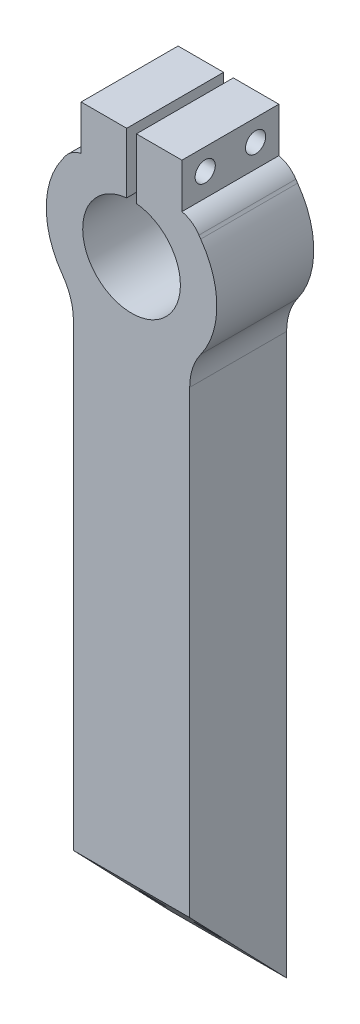
SolidWorks part; units mm, degrees
ref_plane "Front Plane" through (0, 0, 0) normal (0, 0, 1) x (1, 0, 0)
ref_plane "Top Plane" through (0, 0, 0) normal (0, 1, 0) x (1, 0, 0)
ref_plane "Right Plane" through (0, 0, 0) normal (1, 0, 0) x (0, 0, -1)
sketch "Sketch1" plane through (0, 0, 0) normal (0, 0, 1) x (1, 0, 0)
  line L0 (0, 0) -> (30, 0)
  line L1 (55, 0) -> (-55, 0) construction
  line L2 (30, 0) -> (30, 150)
  line L6 (0, -55) -> (0, 55) construction
  line L7 (0, 150) -> (0, 0)
  arc A1 (0, 150) -> (30, 150) centre (15, 166.0935) cw
  dimension "D4" = 22
  dimension "D1" = 150
  dimension "D2" = 150
  dimension "D3" = 30
extrude "Boss-Extrude1" add sketch "Sketch1" along normal blind 25
sketch "Sketch2" plane through (0, 0, 0) normal (1, 0, 0) x (0, 0, -1)
  line L0 (0, 0) -> (-25, 26)
  line L1 (-25, 0) -> (-25, 150) construction
  line L2 (-25, 26) -> (-25, 0)
  line L3 (55, 0) -> (-55, 0) construction
  line L4 (-25, 0) -> (0, 0)
  dimension "D1" = 26
extrude "Cut-Extrude2" cut sketch "Sketch2" along normal through all
sketch "Sketch4" plane through (0, 0, 0) normal (0, 0, 1) x (1, 0, 0)
  line L0 (30, 0) -> (30, 26) construction
  line L1 (55, 0) -> (-55, 0) construction
  line L2 (0, -55) -> (0, 55) construction
  circle A0 centre (8, 13) radius 6.25
  circle A1 centre (22, 13) radius 6.25
  point P8 (0, 0)
  dimension "D5" = 12.5
  dimension "D6" = 12.5
  dimension "D1" = 8
  dimension "D2" = 13
  dimension "D3" = 13
  dimension "D4" = 8
extrude "Cut-Extrude5" cut sketch "Sketch4" along normal blind 3.5
sketch "Sketch5" plane through (0, 0, 0) normal (0, 0, 1) x (1, 0, 0)
  line L0 (0, -55) -> (0, 55) construction
  line L1 (30, 0) -> (30, 26) construction
  line L2 (55, 0) -> (-55, 0) construction
  circle A0 centre (8, 13) radius 2.55
  circle A1 centre (22, 13) radius 2.55
  dimension "D5" = 5.1
  dimension "D6" = 5.1
  dimension "D1" = 8
  dimension "D2" = 8
  dimension "D3" = 13
  dimension "D4" = 13
extrude "Cut-Extrude6" cut sketch "Sketch5" along normal through all
sketch "Sketch6" plane through (0, 0, 0) normal (0, 0, 1) x (1, 0, 0)
  line L0 (0, -13.75) -> (0, 13.75) construction
  circle A0 centre (15, 166.0935) radius 12.6
  arc A1 (30, 150) -> (0, 150) centre (15, 166.0935) ccw construction
  point P2 (0, 0)
  point P5 (0, 0)
  point P7 (0, 0)
  point P11 (15, 188.0935)
  dimension "D1" = 25.2
  dimension "D2" = 15
  dimension "D3" = 22
extrude "Cut-Extrude7" cut sketch "Sketch6" along normal through all
sketch "Sketch8" plane through (0, 0, 0) normal (0, 0, 1) x (1, 0, 0)
  line L0 (0, -13.75) -> (0, 13.75) construction
  line L1 (0, 194.187) -> (30, 194.187)
  line L2 (0, 194.187) -> (0, 182.187)
  line L3 (0, 182.187) -> (30, 182.187)
  line L4 (30, 194.187) -> (30, 182.187)
  arc A0 (30, 150) -> (0, 150) centre (15, 166.0935) ccw construction
  point P9 (0, 0)
  dimension "D1" = 12
extrude "Boss-Extrude2" add sketch "Sketch8" along normal blind 25
fillet "Fillet1" radius 15 4 edges at (0, 150, 12.5) (30, 150, 12.5) (30, 182.187, 12.5) (0, 182.187, 12.5)
fillet "Fillet2" radius 2 2 edges at (30, 194.187, 12.5) (0, 194.187, 12.5)
sketch "Sketch9" plane through (0, 0, 0) normal (1, 0, 0) x (0, 0, -1)
  line L0 (0, 24.2) -> (0, -24.2) construction
  line L1 (-25, 194.187) -> (0, 194.187) construction
  line L2 (-25, 187.7499) -> (-25, 178.9703) construction
  circle A0 centre (-6, 188.687) radius 2.6
  circle A1 centre (-19, 188.687) radius 2.6
  dimension "D1" = 5.2
  dimension "D2" = 6
  dimension "D3" = 5.5
  dimension "D4" = 6
  dimension "D5" = 5.5
extrude "Cut-Extrude8" cut sketch "Sketch9" along normal through all both and the other way through all
sketch "Sketch10" plane through (0, 0, 0) normal (1, 0, 0) x (0, 0, -1)
  line L0 (0, 24.2) -> (0, -24.2) construction
  line L1 (0, 199.187) -> (-25, 199.187)
  line L2 (0, 199.187) -> (0, 182.687)
  line L3 (0, 182.687) -> (-25, 182.687)
  line L4 (-25, 199.187) -> (-25, 182.687)
  line L5 (-25, 187.7499) -> (-25, 178.9703) construction
  line L6 (-25, 194.187) -> (0, 194.187) construction
  dimension "D1" = 16.5
  dimension "D2" = 5
extrude "Cut-Extrude9" cut sketch "Sketch10" against normal blind 25 from offset 2
sketch "Sketch11" plane through (0, 0, 0) normal (1, 0, 0) x (0, 0, -1)
  line L0 (0, 24.2) -> (0, -24.2) construction
  line L1 (0, 199.187) -> (-25, 199.187)
  line L2 (0, 199.187) -> (0, 182.687)
  line L3 (0, 182.687) -> (-25, 182.687)
  line L4 (-25, 199.187) -> (-25, 182.687)
  line L5 (-25, 187.7499) -> (-25, 178.9703) construction
  line L6 (-25, 194.187) -> (0, 194.187) construction
  dimension "D1" = 16.5
  dimension "D2" = 5
extrude "Cut-Extrude10" cut sketch "Sketch11" along normal blind 25 from offset 28
sketch "Sketch13" plane through (0, 0, 0) normal (0, 0, 1) x (1, 0, 0)
  line L0 (28, 194.187) -> (2, 194.187) construction
  line L1 (13.75, 194.187) -> (16.25, 194.187)
  line L2 (13.75, 194.187) -> (13.75, 178.187)
  line L3 (13.75, 178.187) -> (16.25, 178.187)
  line L4 (16.25, 194.187) -> (16.25, 178.187)
  line L5 (0, -13.75) -> (0, 13.75) construction
  dimension "D1" = 2.5
  dimension "D2" = 16
  dimension "D3" = 13.75
extrude "Cut-Extrude11" cut sketch "Sketch13" along normal through all both
fillet "Fillet6" radius 7 2 edges at (30.8803, 182.687, 12.5) (-0.8803, 182.687, 12.5)
